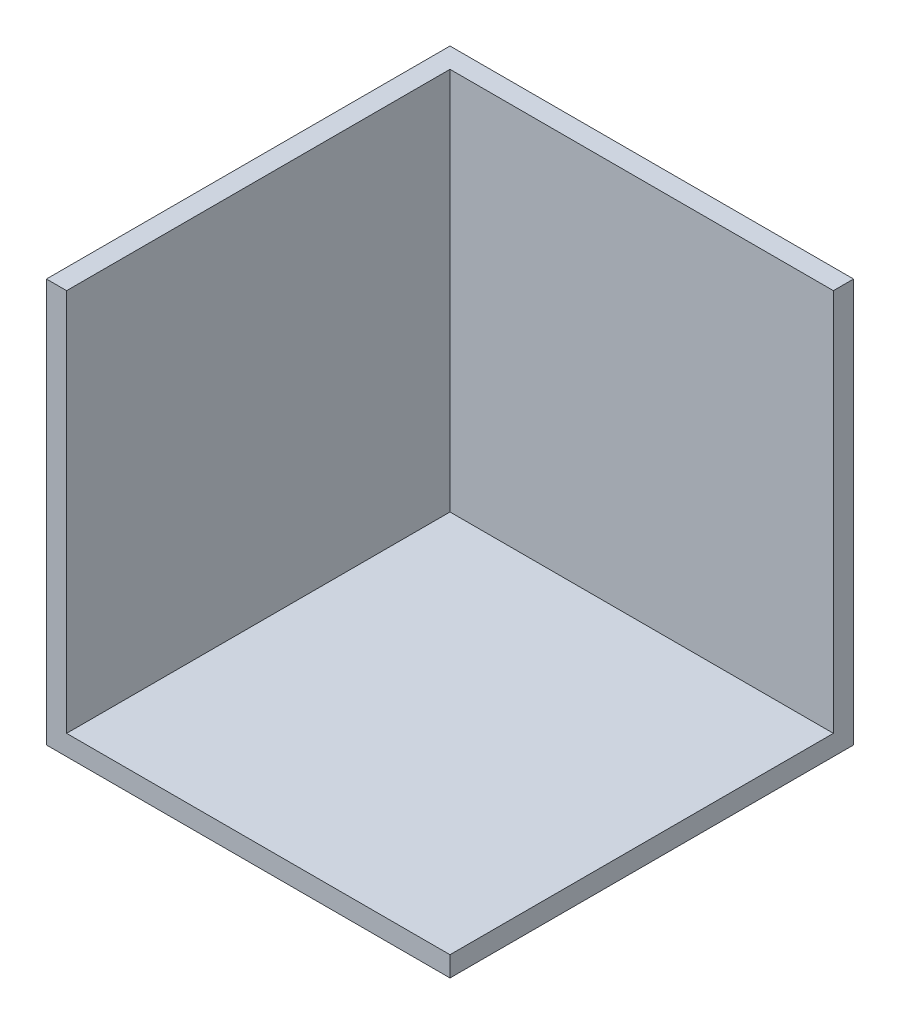
SolidWorks part; units mm, degrees
ref_plane "Plan de face" through (0, 0, 0) normal (0, 0, 1) x (1, 0, 0)
ref_plane "Plan de dessus" through (0, 0, 0) normal (0, 1, 0) x (1, 0, 0)
ref_plane "Plan de droite" through (0, 0, 0) normal (1, 0, 0) x (0, 0, -1)
sketch "Esquisse1" plane through (0, 0, 0) normal (0, 1, 0) x (1, 0, 0)
  line L1 (-8, 8) -> (8, 8)
  line L2 (-8, 8) -> (-8, -8)
  line L3 (-8, -8) -> (8, -8)
  line L4 (8, 8) -> (8, -8)
  line L5 (-8, 8) -> (8, -8) construction
  line L6 (-8, -8) -> (8, 8) construction
  point P0 (0, 0)
  dimension "D1" = 16
extrude "Boss.-Extru.1" add sketch "Esquisse1" along normal blind 16
shell "Coque1" thickness 0.8 removed face at (0, 8, 8) removed face at (8, 8, 0) removed face at (0, 16, 0)
